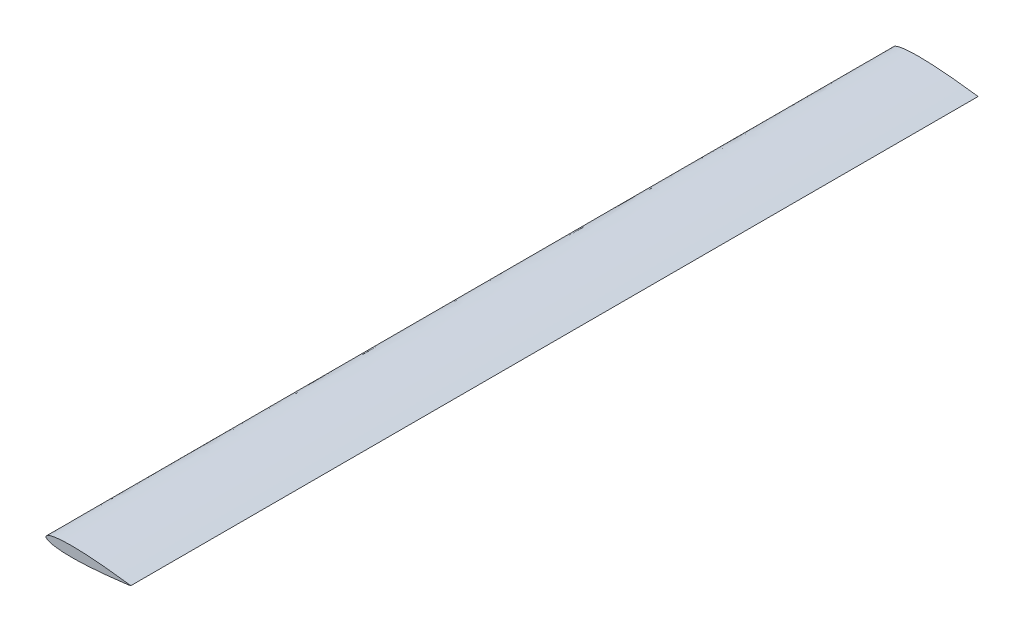
SolidWorks part; units mm, degrees
material "Custom Polymer"
ref_plane "Front Plane" through (0, 0, 0) normal (0, 0, 1) x (1, 0, 0)
ref_plane "Top Plane" through (0, 0, 0) normal (0, 1, 0) x (1, 0, 0)
ref_plane "Right Plane" through (0, 0, 0) normal (1, 0, 0) x (0, 0, -1)
other "Center of Mass"
sketch "Sketch1" plane through (0, 0, 0) normal (0, 0, 1) x (1, 0, 0)
  line L0 (0, 0) -> (1000, 0) construction
  spline S4 degree 3 poles (0.4143, 4.3853) (-0.2008, 0.0001) (0.4094, -4.3857) (2.2543, -8.6603) (5.2707, -12.775) (9.422, -16.7475) (14.6946, -20.592) (21.081, -24.312) (28.5717, -27.9033) (37.1535, -31.3578) (46.8093, -34.6651) (57.5186, -37.8143) (69.2578, -40.7934) (82.0003, -43.5917) (95.717, -46.1976) (110.3762, -48.6018) (125.9441, -50.7943) (142.3846, -52.7677) (159.6593, -54.5151) (177.7281, -56.0316) (196.5487, -57.3135) (216.0775, -58.3589) (236.2687, -59.1679) (257.0752, -59.7419) (278.4485, -60.0841) (300.3387, -60.1994) (322.6946, -60.0941) (345.4641, -59.7758) (368.5941, -59.2535) (392.0304, -58.5372) (415.7184, -57.6376) (439.6028, -56.5665) (463.6278, -55.336) (487.7372, -53.9588) (511.8749, -52.4476) (535.9844, -50.8155) (560.0094, -49.0752) (583.8939, -47.2399) (607.5819, -45.322) (631.0183, -43.3341) (654.1483, -41.2882) (676.9179, -39.1961) (699.2738, -37.0696) (721.1639, -34.9196) (742.5371, -32.7573) (763.3433, -30.5932) (783.5341, -28.438) (803.0622, -26.3022) (821.8821, -24.1954) (839.9497, -22.1283) (857.223, -20.1106) (873.6615, -18.1522) (889.2267, -16.2628) (903.8825, -14.4523) (917.5946, -12.7298) (930.3308, -11.1051) (942.0615, -9.5864) (952.7594, -8.1834) (962.3991, -6.9024) (970.9591, -5.7556) (978.4165, -4.737) (984.7625, -3.8911) (989.9579, -3.1155) (994.0559, -2.7031) (996.8878, -1.9572) (999.5116, -2.4521) (1000.4888, 0.7707) (998.6373, 0.7843) (996.9769, 1.1296) (994.0179, 1.481) (989.9767, 2.0732) (984.7604, 2.7864) (978.4232, 3.6639) (970.9642, 4.6823) (962.4063, 5.8413) (952.7678, 7.1321) (942.0716, 8.5471) (930.3425, 10.0787) (917.6081, 11.7175) (903.8979, 13.4551) (889.2441, 15.2818) (873.6809, 17.1884) (857.2446, 19.1649) (839.9736, 21.2016) (821.9083, 23.2886) (803.0908, 25.4162) (783.565, 27.5735) (763.3766, 29.751) (742.5728, 31.9381) (721.202, 34.124) (699.3143, 36.2981) (676.9607, 38.4492) (654.1935, 40.5664) (631.0658, 42.6379) (607.6316, 44.6517) (583.9456, 46.5957) (560.0632, 48.4573) (536.0401, 50.2241) (511.9324, 51.8829) (487.7965, 53.4207) (463.6885, 54.8245) (439.6649, 56.0815) (415.7818, 57.179) (392.0947, 58.1047) (368.6592, 58.8468) (345.5299, 59.3946) (322.7607, 59.7381) (300.4049, 59.868) (278.5146, 59.7768) (257.1409, 59.4583) (236.3338, 58.9072) (216.1417, 58.1205) (196.6118, 57.0967) (177.7898, 55.8354) (159.7194, 54.3389) (142.4427, 52.6106) (126.0001, 50.6553) (110.4297, 48.48) (95.7679, 46.092) (82.0483, 43.5012) (69.3028, 40.717) (57.5603, 37.7508) (46.8475, 34.6134) (37.188, 31.3167) (28.6024, 27.8718) (21.1078, 24.2887) (14.7173, 20.5758) (9.4405, 16.7371) (5.2848, 12.7691) (2.2639, 8.6578) (0.4143, 4.3853) (-0.2008, 0.0001) (0.4094, -4.3857) knots -0.006774 -0.004322 -0.002107 0 0.002107 0.004322 0.006774 0.009559 0.012737 0.016346 0.02041 0.02494 0.02994 0.03541 0.041346 0.047742 0.054587 0.061871 0.06958 0.077699 0.086213 0.095105 0.104356 0.113946 0.123856 0.134064 0.144547 0.155282 0.166246 0.177414 0.188761 0.20026 0.211886 0.223612 0.23541 0.247253 0.259115 0.270966 0.28278 0.294528 0.306184 0.31772 0.329108 0.340322 0.351336 0.362124 0.37266 0.382919 0.392878 0.402513 0.4118 0.42072 0.429249 0.437368 0.445058 0.452301 0.459079 0.465376 0.471177 0.476469 0.481238 0.485474 0.489166 0.492305 0.494884 0.496896 0.498337 0.499202 0.500509 0.500798 0.501663 0.503104 0.505116 0.507695 0.510834 0.514526 0.518762 0.523531 0.528823 0.534624 0.540921 0.547699 0.554942 0.562632 0.570751 0.57928 0.5882 0.597487 0.607122 0.617081 0.62734 0.637876 0.648664 0.659678 0.670892 0.68228 0.693816 0.705472 0.71722 0.729034 0.740885 0.752747 0.76459 0.776388 0.788114 0.79974 0.811239 0.822586 0.833754 0.844718 0.855453 0.865936 0.876144 0.886054 0.895644 0.904895 0.913787 0.922301 0.93042 0.938129 0.945413 0.952258 0.958654 0.96459 0.97006 0.97506 0.97959 0.983654 0.987263 0.990441 0.993226 0.995678 0.997893 1 1.002107 1.004322 1.006774 only from (0, 0) to (0, 0)
  dimension "D1" = 1000
extrude "Boss-Extrude1" add sketch "Sketch1" along normal blind 10000
sketch "Sketch3" plane through (0, 0, 0) normal (0, 0, -1) x (-1, 0, 0)
  line L0 (-46.6725, -5.2388) -> (-46.6725, 5.2387) construction
  line L1 (-27.6225, 5.2388) -> (-27.6225, -5.2388) construction
  line L2 (-7.7788, -3.8184) -> (-7.7788, 3.8184) construction
  line L3 (-71.2788, 3.6758) -> (-71.2788, -3.6758) construction
  line L4 (-46.6725, -5.2388) -> (-46.6725, 5.2387)
  line L5 (-27.6225, 5.2388) -> (-27.6225, -5.2388)
  line L6 (-7.7788, -3.8184) -> (-7.7788, 3.8184)
  line L7 (-71.2788, 3.6758) -> (-71.2788, -3.6758)
  arc A0 (-71.2788, -3.6758) -> (-46.6725, -5.2388) centre (-26.6642, 504.2394) ccw construction
  arc A1 (-46.6725, 5.2387) -> (-71.2788, 3.6758) centre (-26.6642, -504.2394) ccw construction
  circle A2 centre (-35.56, 0) radius 3.1433 construction
  circle A3 centre (-3.0163, 0) radius 2.9766 construction
  arc A4 (-71.2788, -3.6758) -> (-46.6725, -5.2388) centre (-26.6642, 504.2394) ccw
  arc A5 (-46.6725, 5.2387) -> (-71.2788, 3.6758) centre (-26.6642, -504.2394) ccw
  circle A6 centre (-35.56, 0) radius 3.1433
  circle A7 centre (-3.0163, 0) radius 2.9766
  circle A8 centre (-21.2725, 0) radius 3.9688
  circle A9 centre (-53.0225, 0) radius 3.9687
  spline S0 degree 3 poles (8.8377, -0.5571) (8.9155, 0) (8.8377, 0.5571) (8.603, 1.1001) (8.2195, 1.6226) (7.6918, 2.127) (7.0217, 2.615) (6.2101, 3.0872) (5.2582, 3.5429) (4.1677, 3.9812) (2.9408, 4.4007) (1.58, 4.8) (0.0884, 5.1777) (-1.5306, 5.5323) (-3.2734, 5.8624) (-5.1359, 6.1668) (-7.1139, 6.4442) (-9.2026, 6.6938) (-11.3974, 6.9146) (-13.693, 7.106) (-16.0841, 7.2675) (-18.5652, 7.3989) (-21.1304, 7.5003) (-23.7737, 7.5718) (-26.4891, 7.6137) (-29.2701, 7.6269) (-32.1103, 7.6119) (-35.0029, 7.5699) (-37.9414, 7.5019) (-40.9188, 7.4093) (-43.9281, 7.2933) (-46.9624, 7.1556) (-50.0145, 6.9976) (-53.0773, 6.8209) (-56.1437, 6.6272) (-59.2065, 6.4182) (-62.2586, 6.1954) (-65.2928, 5.9606) (-68.3021, 5.7153) (-71.2794, 5.4611) (-74.2178, 5.1995) (-77.1103, 4.9321) (-79.9503, 4.6604) (-82.7312, 4.3857) (-85.4463, 4.1095) (-88.0894, 3.8332) (-90.6544, 3.5579) (-93.1352, 3.2852) (-95.5259, 3.0163) (-97.8211, 2.7524) (-100.0154, 2.4948) (-102.1037, 2.2449) (-104.081, 2.0038) (-105.9428, 1.7727) (-107.6847, 1.5529) (-109.3027, 1.3456) (-110.7928, 1.1519) (-112.1518, 0.9728) (-113.3764, 0.8095) (-114.4637, 0.6629) (-115.4114, 0.534) (-116.2166, 0.423) (-116.8793, 0.3328) (-117.3928, 0.2578) (-117.7687, 0.2134) (-117.9797, 0.1696) (-118.2149, 0.168) (-118.091, -0.2415) (-117.7576, -0.1788) (-117.3979, -0.2737) (-116.8773, -0.3264) (-116.2173, -0.4253) (-115.4111, -0.5332) (-114.4638, -0.6632) (-113.3764, -0.8095) (-112.1518, -0.9729) (-110.7928, -1.1519) (-109.3027, -1.3456) (-107.6847, -1.5529) (-105.9428, -1.7727) (-104.081, -2.0038) (-102.1037, -2.2449) (-100.0154, -2.4948) (-97.8211, -2.7524) (-95.5259, -3.0163) (-93.1352, -3.2852) (-90.6544, -3.5579) (-88.0894, -3.8332) (-85.4463, -4.1095) (-82.7312, -4.3857) (-79.9503, -4.6604) (-77.1103, -4.9321) (-74.2178, -5.1995) (-71.2794, -5.4611) (-68.3021, -5.7153) (-65.2928, -5.9606) (-62.2586, -6.1954) (-59.2065, -6.4182) (-56.1437, -6.6272) (-53.0773, -6.8209) (-50.0145, -6.9976) (-46.9624, -7.1556) (-43.9281, -7.2933) (-40.9188, -7.4093) (-37.9414, -7.5019) (-35.0029, -7.5699) (-32.1103, -7.6119) (-29.2701, -7.6269) (-26.4891, -7.6137) (-23.7737, -7.5718) (-21.1304, -7.5003) (-18.5652, -7.3989) (-16.0841, -7.2675) (-13.693, -7.106) (-11.3974, -6.9146) (-9.2026, -6.6938) (-7.1139, -6.4442) (-5.1359, -6.1668) (-3.2734, -5.8624) (-1.5306, -5.5323) (0.0884, -5.1777) (1.58, -4.8) (2.9408, -4.4007) (4.1677, -3.9812) (5.2582, -3.5429) (6.2101, -3.0872) (7.0217, -2.615) (7.6918, -2.127) (8.2195, -1.6226) (8.603, -1.1001) (8.8377, -0.5571) (8.9155, 0) (8.8377, 0.5571) knots -0.006774 -0.004322 -0.002107 0 0.002107 0.004322 0.006774 0.009559 0.012737 0.016346 0.02041 0.02494 0.02994 0.03541 0.041346 0.047742 0.054587 0.061871 0.06958 0.077699 0.086213 0.095105 0.104356 0.113946 0.123856 0.134064 0.144547 0.155282 0.166246 0.177414 0.188761 0.20026 0.211886 0.223612 0.23541 0.247253 0.259115 0.270966 0.28278 0.294528 0.306184 0.31772 0.329108 0.340322 0.351336 0.362124 0.37266 0.382919 0.392878 0.402513 0.4118 0.42072 0.429249 0.437368 0.445058 0.452301 0.459079 0.465376 0.471177 0.476469 0.481238 0.485474 0.489166 0.492305 0.494884 0.496896 0.498337 0.499202 0.499491 0.500798 0.501663 0.503104 0.505116 0.507695 0.510834 0.514526 0.518762 0.523531 0.528823 0.534624 0.540921 0.547699 0.554942 0.562632 0.570751 0.57928 0.5882 0.597487 0.607122 0.617081 0.62734 0.637876 0.648664 0.659678 0.670892 0.68228 0.693816 0.705472 0.71722 0.729034 0.740885 0.752747 0.76459 0.776388 0.788114 0.79974 0.811239 0.822586 0.833754 0.844718 0.855453 0.865936 0.876144 0.886054 0.895644 0.904895 0.913787 0.922301 0.93042 0.938129 0.945413 0.952258 0.958654 0.96459 0.97006 0.97506 0.97959 0.983654 0.987263 0.990441 0.993226 0.995678 0.997893 1 1.002107 1.004322 1.006774 only from (8.89, 0) to (8.89, 0) construction
  spline S1 degree 3 poles (-27.6225, 5.2388) (-20.0778, 5.0313) (-13.2778, 4.5445) (-7.7788, 3.8184) knots 0 0 0 0 1 1 1 1 weights 1 0.972728 0.972728 1 construction
  spline S2 degree 3 poles (-27.6225, -5.2388) (-20.0778, -5.0313) (-13.2778, -4.5445) (-7.7788, -3.8184) knots 0 0 0 0 1 1 1 1 weights 1 0.972728 0.972728 1 construction
  spline S3 degree 3 poles (8.8377, -0.5571) (8.9155, 0) (8.8377, 0.5571) (8.603, 1.1001) (8.2195, 1.6226) (7.6918, 2.127) (7.0217, 2.615) (6.2101, 3.0872) (5.2582, 3.5429) (4.1677, 3.9812) (2.9408, 4.4007) (1.58, 4.8) (0.0884, 5.1777) (-1.5306, 5.5323) (-3.2734, 5.8624) (-5.1359, 6.1668) (-7.1139, 6.4442) (-9.2026, 6.6938) (-11.3974, 6.9146) (-13.693, 7.106) (-16.0841, 7.2675) (-18.5652, 7.3989) (-21.1304, 7.5003) (-23.7737, 7.5718) (-26.4891, 7.6137) (-29.2701, 7.6269) (-32.1103, 7.6119) (-35.0029, 7.5699) (-37.9414, 7.5019) (-40.9188, 7.4093) (-43.9281, 7.2933) (-46.9624, 7.1556) (-50.0145, 6.9976) (-53.0773, 6.8209) (-56.1437, 6.6272) (-59.2065, 6.4182) (-62.2586, 6.1954) (-65.2928, 5.9606) (-68.3021, 5.7153) (-71.2794, 5.4611) (-74.2178, 5.1995) (-77.1103, 4.9321) (-79.9503, 4.6604) (-82.7312, 4.3857) (-85.4463, 4.1095) (-88.0894, 3.8332) (-90.6544, 3.5579) (-93.1352, 3.2852) (-95.5259, 3.0163) (-97.8211, 2.7524) (-100.0154, 2.4948) (-102.1037, 2.2449) (-104.081, 2.0038) (-105.9428, 1.7727) (-107.6847, 1.5529) (-109.3027, 1.3456) (-110.7928, 1.1519) (-112.1518, 0.9728) (-113.3764, 0.8095) (-114.4637, 0.6629) (-115.4114, 0.534) (-116.2166, 0.423) (-116.8793, 0.3328) (-117.3928, 0.2578) (-117.7687, 0.2134) (-117.9797, 0.1696) (-118.2149, 0.168) (-118.091, -0.2415) (-117.7576, -0.1788) (-117.3979, -0.2737) (-116.8773, -0.3264) (-116.2173, -0.4253) (-115.4111, -0.5332) (-114.4638, -0.6632) (-113.3764, -0.8095) (-112.1518, -0.9729) (-110.7928, -1.1519) (-109.3027, -1.3456) (-107.6847, -1.5529) (-105.9428, -1.7727) (-104.081, -2.0038) (-102.1037, -2.2449) (-100.0154, -2.4948) (-97.8211, -2.7524) (-95.5259, -3.0163) (-93.1352, -3.2852) (-90.6544, -3.5579) (-88.0894, -3.8332) (-85.4463, -4.1095) (-82.7312, -4.3857) (-79.9503, -4.6604) (-77.1103, -4.9321) (-74.2178, -5.1995) (-71.2794, -5.4611) (-68.3021, -5.7153) (-65.2928, -5.9606) (-62.2586, -6.1954) (-59.2065, -6.4182) (-56.1437, -6.6272) (-53.0773, -6.8209) (-50.0145, -6.9976) (-46.9624, -7.1556) (-43.9281, -7.2933) (-40.9188, -7.4093) (-37.9414, -7.5019) (-35.0029, -7.5699) (-32.1103, -7.6119) (-29.2701, -7.6269) (-26.4891, -7.6137) (-23.7737, -7.5718) (-21.1304, -7.5003) (-18.5652, -7.3989) (-16.0841, -7.2675) (-13.693, -7.106) (-11.3974, -6.9146) (-9.2026, -6.6938) (-7.1139, -6.4442) (-5.1359, -6.1668) (-3.2734, -5.8624) (-1.5306, -5.5323) (0.0884, -5.1777) (1.58, -4.8) (2.9408, -4.4007) (4.1677, -3.9812) (5.2582, -3.5429) (6.2101, -3.0872) (7.0217, -2.615) (7.6918, -2.127) (8.2195, -1.6226) (8.603, -1.1001) (8.8377, -0.5571) (8.9155, 0) (8.8377, 0.5571) knots -0.006774 -0.004322 -0.002107 0 0.002107 0.004322 0.006774 0.009559 0.012737 0.016346 0.02041 0.02494 0.02994 0.03541 0.041346 0.047742 0.054587 0.061871 0.06958 0.077699 0.086213 0.095105 0.104356 0.113946 0.123856 0.134064 0.144547 0.155282 0.166246 0.177414 0.188761 0.20026 0.211886 0.223612 0.23541 0.247253 0.259115 0.270966 0.28278 0.294528 0.306184 0.31772 0.329108 0.340322 0.351336 0.362124 0.37266 0.382919 0.392878 0.402513 0.4118 0.42072 0.429249 0.437368 0.445058 0.452301 0.459079 0.465376 0.471177 0.476469 0.481238 0.485474 0.489166 0.492305 0.494884 0.496896 0.498337 0.499202 0.499491 0.500798 0.501663 0.503104 0.505116 0.507695 0.510834 0.514526 0.518762 0.523531 0.528823 0.534624 0.540921 0.547699 0.554942 0.562632 0.570751 0.57928 0.5882 0.597487 0.607122 0.617081 0.62734 0.637876 0.648664 0.659678 0.670892 0.68228 0.693816 0.705472 0.71722 0.729034 0.740885 0.752747 0.76459 0.776388 0.788114 0.79974 0.811239 0.822586 0.833754 0.844718 0.855453 0.865936 0.876144 0.886054 0.895644 0.904895 0.913787 0.922301 0.93042 0.938129 0.945413 0.952258 0.958654 0.96459 0.97006 0.97506 0.97959 0.983654 0.987263 0.990441 0.993226 0.995678 0.997893 1 1.002107 1.004322 1.006774 only from (8.89, 0) to (8.89, 0)
  spline S4 degree 3 poles (-27.6225, 5.2388) (-20.0778, 5.0313) (-13.2778, 4.5445) (-7.7788, 3.8184) knots 0 0 0 0 1 1 1 1 weights 1 0.972728 0.972728 1
  spline S5 degree 3 poles (-27.6225, -5.2388) (-20.0778, -5.0313) (-13.2778, -4.5445) (-7.7788, -3.8184) knots 0 0 0 0 1 1 1 1 weights 1 0.972728 0.972728 1
  dimension "D2" = 7.9375
  dimension "D3" = 7.9375
  dimension "D1" = 6.35
  dimension "D4" = 6.35
extrude "Boss-Extrude2" [suppressed] add sketch "Sketch3" along normal blind 6.35
pattern_linear "LPattern1" [suppressed] count 3 spacing 69.85 of bodies 102
sketch "Sketch5" [suppressed] plane through (0, 0, -139.7) normal (0, 0, 1) x (1, 0, 0)
  line L2 (71.2787, -3.6758) -> (71.2788, 3.6758)
  line L3 (46.6725, 5.2387) -> (46.6725, -5.2388)
  line L4 (71.2787, -3.6758) -> (71.2788, 3.6758)
  line L5 (46.6725, 5.2387) -> (46.6725, -5.2388)
  arc A2 (46.6725, -5.2388) -> (71.2787, -3.6758) centre (26.6642, 504.2394) ccw
  arc A3 (71.2788, 3.6758) -> (46.6725, 5.2387) centre (26.6642, -504.2394) ccw
  arc A4 (46.6725, -5.2388) -> (71.2787, -3.6758) centre (26.6642, 504.2394) ccw
  arc A5 (71.2788, 3.6758) -> (46.6725, 5.2387) centre (26.6642, -504.2394) ccw
  dimension "D1" = 0
extrude "Cut-Extrude1" [suppressed] cut sketch "Sketch5" against normal blind 6.35
sketch "Sketch6" [suppressed] plane through (0, 0, -139.7) normal (0, 0, 1) x (1, 0, 0)
  line L2 (27.6225, -5.2388) -> (27.6225, 5.2388)
  line L3 (7.7788, 3.8184) -> (7.7788, -3.8184)
  line L4 (27.6225, -5.2388) -> (27.6225, 5.2388)
  line L5 (7.7788, 3.8184) -> (7.7788, -3.8184)
  spline S2 degree 3 poles (7.7788, -3.8184) (13.2778, -4.5445) (20.0778, -5.0313) (27.6225, -5.2388) knots 0 0 0 0 1 1 1 1 weights 1 0.972728 0.972728 1
  spline S3 degree 3 poles (27.6225, 5.2388) (20.0778, 5.0313) (13.2778, 4.5445) (7.7788, 3.8184) knots 0 0 0 0 1 1 1 1 weights 1 0.972728 0.972728 1
  spline S4 degree 3 poles (7.7788, -3.8184) (13.2778, -4.5445) (20.0778, -5.0313) (27.6225, -5.2388) knots 0 0 0 0 1 1 1 1 weights 1 0.972728 0.972728 1
  spline S5 degree 3 poles (27.6225, 5.2388) (20.0778, 5.0313) (13.2778, 4.5445) (7.7788, 3.8184) knots 0 0 0 0 1 1 1 1 weights 1 0.972728 0.972728 1
  dimension "D1" = 0
extrude "Cut-Extrude2" [suppressed] cut sketch "Sketch6" against normal blind 6.35
sketch "Sketch8" [suppressed] plane through (0, 0, 609.6) normal (0, 0, 1) x (1, 0, 0)
  line L0 (35.56, 0) -> (-8.89, 0) construction
  spline S0 degree 3 poles (-8.8377, 0.5571) (-8.9155, 0) (-8.8377, -0.5571) (-8.603, -1.1001) (-8.2195, -1.6226) (-7.6918, -2.127) (-7.0217, -2.615) (-6.2101, -3.0872) (-5.2582, -3.5429) (-4.1677, -3.9812) (-2.9408, -4.4007) (-1.58, -4.8) (-0.0884, -5.1777) (1.5306, -5.5323) (3.2734, -5.8624) (5.1359, -6.1668) (7.1139, -6.4442) (9.2026, -6.6938) (11.3974, -6.9146) (13.693, -7.106) (16.0841, -7.2675) (18.5652, -7.3989) (21.1304, -7.5003) (23.7737, -7.5718) (26.4891, -7.6137) (29.2701, -7.6269) (32.1103, -7.6119) (35.0029, -7.5699) (37.9414, -7.5019) (40.9188, -7.4093) (43.9281, -7.2933) (46.9624, -7.1556) (50.0145, -6.9976) (53.0773, -6.8209) (56.1437, -6.6272) (59.2065, -6.4182) (62.2586, -6.1954) (65.2928, -5.9606) (68.3021, -5.7153) (71.2794, -5.4611) (74.2178, -5.1995) (77.1103, -4.9321) (79.9503, -4.6604) (82.7312, -4.3857) (85.4463, -4.1095) (88.0894, -3.8332) (90.6544, -3.5579) (93.1352, -3.2852) (95.5259, -3.0163) (97.8211, -2.7524) (100.0154, -2.4948) (102.1037, -2.2449) (104.081, -2.0038) (105.9428, -1.7727) (107.6847, -1.5529) (109.3027, -1.3456) (110.7928, -1.1519) (112.1518, -0.9729) (113.3764, -0.8095) (114.4638, -0.6632) (115.4111, -0.5332) (116.2173, -0.4253) (116.8773, -0.3264) (117.3979, -0.2737) (117.7576, -0.1788) (118.091, -0.2415) (118.2149, 0.168) (117.9797, 0.1696) (117.7687, 0.2134) (117.3928, 0.2578) (116.8793, 0.3328) (116.2166, 0.423) (115.4114, 0.534) (114.4637, 0.6629) (113.3764, 0.8095) (112.1518, 0.9728) (110.7928, 1.1519) (109.3027, 1.3456) (107.6847, 1.5529) (105.9428, 1.7727) (104.081, 2.0038) (102.1037, 2.2449) (100.0154, 2.4948) (97.8211, 2.7524) (95.5259, 3.0163) (93.1352, 3.2852) (90.6544, 3.5579) (88.0894, 3.8332) (85.4463, 4.1095) (82.7312, 4.3857) (79.9503, 4.6604) (77.1103, 4.9321) (74.2178, 5.1995) (71.2794, 5.4611) (68.3021, 5.7153) (65.2928, 5.9606) (62.2586, 6.1954) (59.2065, 6.4182) (56.1437, 6.6272) (53.0773, 6.8209) (50.0145, 6.9976) (46.9624, 7.1556) (43.9281, 7.2933) (40.9188, 7.4093) (37.9414, 7.5019) (35.0029, 7.5699) (32.1103, 7.6119) (29.2701, 7.6269) (26.4891, 7.6137) (23.7737, 7.5718) (21.1304, 7.5003) (18.5652, 7.3989) (16.0841, 7.2675) (13.693, 7.106) (11.3974, 6.9146) (9.2026, 6.6938) (7.1139, 6.4442) (5.1359, 6.1668) (3.2734, 5.8624) (1.5306, 5.5323) (-0.0884, 5.1777) (-1.58, 4.8) (-2.9408, 4.4007) (-4.1677, 3.9812) (-5.2582, 3.5429) (-6.2101, 3.0872) (-7.0217, 2.615) (-7.6918, 2.127) (-8.2195, 1.6226) (-8.603, 1.1001) (-8.8377, 0.5571) (-8.9155, 0) (-8.8377, -0.5571) knots -0.006774 -0.004322 -0.002107 0 0.002107 0.004322 0.006774 0.009559 0.012737 0.016346 0.02041 0.02494 0.02994 0.03541 0.041346 0.047742 0.054587 0.061871 0.06958 0.077699 0.086213 0.095105 0.104356 0.113946 0.123856 0.134064 0.144547 0.155282 0.166246 0.177414 0.188761 0.20026 0.211886 0.223612 0.23541 0.247253 0.259115 0.270966 0.28278 0.294528 0.306184 0.31772 0.329108 0.340322 0.351336 0.362124 0.37266 0.382919 0.392878 0.402513 0.4118 0.42072 0.429249 0.437368 0.445058 0.452301 0.459079 0.465376 0.471177 0.476469 0.481238 0.485474 0.489166 0.492305 0.494884 0.496896 0.498337 0.499202 0.500509 0.500798 0.501663 0.503104 0.505116 0.507695 0.510834 0.514526 0.518762 0.523531 0.528823 0.534624 0.540921 0.547699 0.554942 0.562632 0.570751 0.57928 0.5882 0.597487 0.607122 0.617081 0.62734 0.637876 0.648664 0.659678 0.670892 0.68228 0.693816 0.705472 0.71722 0.729034 0.740885 0.752747 0.76459 0.776388 0.788114 0.79974 0.811239 0.822586 0.833754 0.844718 0.855453 0.865936 0.876144 0.886054 0.895644 0.904895 0.913787 0.922301 0.93042 0.938129 0.945413 0.952258 0.958654 0.96459 0.97006 0.97506 0.97959 0.983654 0.987263 0.990441 0.993226 0.995678 0.997893 1 1.002107 1.004322 1.006774 only from (-8.89, 0) to (-8.89, 0) construction
